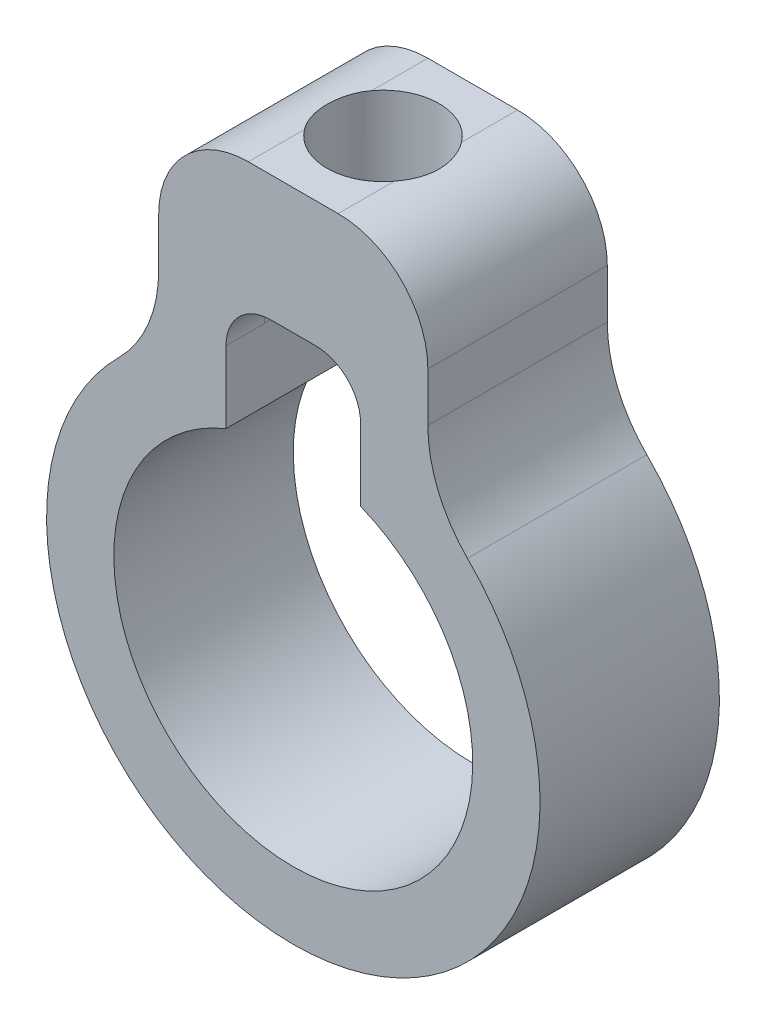
SolidWorks part; units mm, degrees
note: The reader was unsure of these and kept them because the rebuilt part matched: shared geometry of "ｽｹｯﾁ1<3>".
material "2014 合金"
ref_plane "正面" through (0, 0, 0) normal (0, 0, 1) x (1, 0, 0)
ref_plane "平面" through (0, 0, 0) normal (0, 1, 0) x (1, 0, 0)
ref_plane "右側面" through (0, 0, 0) normal (1, 0, 0) x (0, 0, -1)
sketch "ｽｹｯﾁ1" plane through (0, 0, 0) normal (0, 0, 1) x (1, 0, 0)
  line L1 (-1.5, 3.7081) -> (1.5, 3.7081)
  line L2 (-1.5, 3.7081) -> (-1.5, 6.3081)
  line L3 (-1.5, 6.3081) -> (1.5, 6.3081)
  line L4 (1.5, 3.7081) -> (1.5, 6.3081)
  line L5 (-1.5, 3.7081) -> (1.5, 3.7081) construction
  line L6 (-1.5, 3.7081) -> (-1.5, 5.2081) construction
  line L7 (-1.5, 5.2081) -> (1.5, 5.2081) construction
  line L8 (1.5, 3.7081) -> (1.5, 5.2081) construction
  line L9 (-3, 4.6098) -> (3, 4.6098)
  line L10 (-3, 4.6098) -> (-3, 9.1098)
  line L11 (-3, 9.1098) -> (3, 9.1098)
  line L12 (3, 4.6098) -> (3, 9.1098)
  circle A0 centre (0, 0) radius 4
  circle A1 centre (0, 0) radius 5.5
  circle A3 centre (0, 0) radius 10 construction
  dimension "D1" = 8
  dimension "D6" = 11
  dimension "D10" = 20
  dimension "D2" = 2.6
  dimension "D3" = 3
  dimension "D4" = 1.5
  dimension "D5" = 3
  dimension "D7" = 4.5
  dimension "D8" = 6
  dimension "D9" = 2.8017
extrude "ﾎﾞｽ - 押し出し1" add sketch "ｽｹｯﾁ1" along normal blind 4 contours L11 L12 L9 L10 | A1
extrude "ｶｯﾄ - 押し出し1" cut sketch "ｽｹｯﾁ1<3>" along normal through all contours L3 L4 L1 L2 | A0
sketch "ｽｹｯﾁ1<3>" plane through (0, 0, 0) normal (0, 0, 1) x (1, 0, 0) same geometry as "ｽｹｯﾁ1"
sketch "ｽｹｯﾁ2" plane through (0, 9.1098, 0) normal (0, 1, 0) x (1, 0, 0)
  line L0 (-3, 0) -> (3, 0) construction
  circle A0 centre (0, -2) radius 1.25
  dimension "D1" = 2.5
  dimension "D2" = 2
extrude "ｶｯﾄ - 押し出し2" cut sketch "ｽｹｯﾁ2" against normal up to next
fillet "ﾌｨﾚｯﾄ1" radius 1 2 edges at (1.5, 6.3081, 2) (-1.5, 6.3081, 2)
fillet "ﾌｨﾚｯﾄ2" radius 2 2 edges at (3, 9.1098, 2) (-3, 9.1098, 2)
fillet "ﾌｨﾚｯﾄ3" radius 3 2 edges at (3, 4.6098, 2) (-3, 4.6098, 2)
